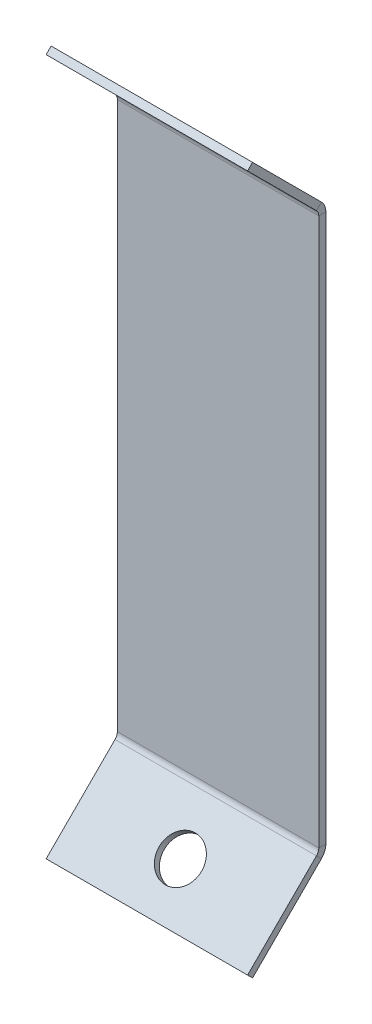
SolidWorks part; units mm, degrees
note: The reader was unsure of these and kept them because the rebuilt part matched: flange length of "Edge-Flange1", "Edge-Flange2".
ref_plane "Front Plane" through (0, 0, 0) normal (0, 0, 1) x (1, 0, 0)
ref_plane "Top Plane" through (0, 0, 0) normal (0, 1, 0) x (1, 0, 0)
ref_plane "Right Plane" through (0, 0, 0) normal (1, 0, 0) x (0, 0, -1)
sketch "Sketch1" plane through (0, 0, 0) normal (0, 0, 1) x (1, 0, 0)
  line L0 (10, 27.5) -> (-10, -27.5) construction
  line L1 (10, 27.5) -> (-10, 27.5)
  line L2 (10, 27.5) -> (10, -27.5)
  line L3 (10, -27.5) -> (-10, -27.5)
  line L4 (-10, 27.5) -> (-10, -27.5)
  point P4 (0, 0)
  dimension "D1" = 20
  dimension "D2" = 55
base flange "Base-Flange1" sketch "Sketch1" thickness 0.7 reverse thickness direction no parameters "D1"=0.8
edge flange "Edge-Flange1" sketch "Sketch8" flange angle 135 flange length 10 flange position material outside bend radius 0.8 thickness 0.7 parameters "D1"=3, "D6"=10
sketch "Sketch8" plane through (0, -27.5, 0) normal (0, -0.7071, -0.7071) x (1, 0, 0)
  line L0 (-10, 0) -> (10, 0) construction
  line L1 (-10, 0) -> (10, 0)
  line L2 (-10, 0) -> (-10, 10)
  line L3 (-10, 10) -> (10, 10)
  line L4 (10, 10) -> (10, 0)
bend "EdgeBend1" bend radius 0.8 bend angle 45 parameters "D5"=1
edge flange "Edge-Flange2" sketch "Sketch11" flange angle 135 flange length 10 flange position material outside bend radius 0.8 thickness 0.7 parameters "D1"=3, "D6"=10
sketch "Sketch11" plane through (0, 27.5, 0) normal (0, 0.7071, -0.7071) x (-1, 0, 0)
  line L2 (-10, 0) -> (-10, 10)
  line L3 (-10, 10) -> (10, 10)
  line L4 (10, 10) -> (10, 0)
  line L5 (-10, 0) -> (10, 0) construction
  line L6 (-10, 0) -> (10, 0)
bend "EdgeBend2" bend radius 0.8 bend angle 45 parameters "D5"=2
hole_wizard "#19 (0.166) Diameter Slot1" positions "Sketch13" profile "Sketch12" size "#19" standard "ANSI Inch" slot yes end condition through all
sketch "Sketch13" plane through (0, -13.75, -13.75) normal (0, 0.7071, 0.7071) x (1, 0, 0)
  point P0 (0, -24.7388)
sketch "Sketch12" plane through (0, -31.243, 3.743) normal (1, 0, 0) x (0, -0.7071, 0.7071)
  line L0 (0, 0) -> (0, 5.845)
  line L1 (0, 5.845) -> (2.1082, 5.845)
  line L2 (2.1082, 5.845) -> (2.1082, 0)
  line L5 (2.1082, 0) -> (0, 0)
  line L11 (0, -6.35) -> (0, 107.95) construction
  dimension "Thru Hole Dia." = 4.2164
  dimension "Thru Hole Depth" = 5.845
hole_wizard "#19 (0.166) Diameter Slot2" positions "Sketch15" profile "Sketch14" size "#19" standard "ANSI Inch" slot yes end condition through all
sketch "Sketch15" plane through (0, 13.75, -13.75) normal (0, -0.7071, 0.7071) x (1, 0, 0)
  point P0 (0, 24.9402)
sketch "Sketch14" plane through (0, 31.3854, 3.8854) normal (1, 0, 0) x (0, -0.7071, -0.7071)
  line L0 (0, 0) -> (0, 5.845)
  line L1 (0, 5.845) -> (2.1082, 5.845)
  line L2 (2.1082, 5.845) -> (2.1082, 0)
  line L5 (2.1082, 0) -> (0, 0)
  line L11 (0, -6.35) -> (0, 107.95) construction
  dimension "Thru Hole Dia." = 4.2164
  dimension "Thru Hole Depth" = 5.845
sketch "Bend-Lines1" plane through (0, 0, 0) normal (0, 1, 0) x (1, 0, 0)
sketch "Bounding-Box1" plane through (0, 0, 0) normal (0, 1, 0) x (1, 0, 0)
sheet metal parameters "Sheet-Metal1" thickness 0.7 parameters "D1"=3
flat pattern "Flat-Pattern1" [suppressed]
sketch "Bend-Lines2" plane through (0, 0, 0) normal (0, 1, 0) x (1, 0, 0)
sketch "Bounding-Box2" [suppressed] plane through (0, 0, 0) normal (0, 1, 0) x (1, 0, 0)
sheet metal parameters "Sheet-Metal2" thickness 0.7 parameters "D1"=3
flat pattern "Flat-Pattern1" [suppressed]
sketch "Bend-Lines2" plane through (0, 0, 0) normal (0, 1, 0) x (1, 0, 0)
sketch "Bounding-Box2" [suppressed] plane through (0, 0, 0) normal (0, 1, 0) x (1, 0, 0)
bend of the flat pattern "Flatten-<EdgeBend1>1"
sheet metal parameters "Sheet-Metal3" thickness 0.7 parameters "D1"=3
flat pattern "Flat-Pattern1" [suppressed]
sketch "Bend-Lines2" plane through (0, 0, 0) normal (0, 1, 0) x (1, 0, 0)
sketch "Bounding-Box2" [suppressed] plane through (0, 0, 0) normal (0, 1, 0) x (1, 0, 0)
bend of the flat pattern "Flatten-<EdgeBend1>1"
bend of the flat pattern "Flatten-<EdgeBend2>1"
sheet metal parameters "Sheet-Metal4" thickness 0.7 parameters "D1"=3
flat pattern "Flat-Pattern1" [suppressed]
sketch "Bend-Lines2" plane through (0, 0, 0) normal (0, 1, 0) x (1, 0, 0)
sketch "Bounding-Box2" [suppressed] plane through (0, 0, 0) normal (0, 1, 0) x (1, 0, 0)
bend of the flat pattern "Flatten-<EdgeBend1>1"
bend of the flat pattern "Flatten-<EdgeBend2>1"
sheet metal parameters "Sheet-Metal5" thickness 0.7 parameters "D1"=3
flat pattern "Flat-Pattern1" [suppressed]
sketch "Bend-Lines2" plane through (0, 0, 0) normal (0, 1, 0) x (1, 0, 0)
sketch "Bounding-Box2" [suppressed] plane through (0, 0, 0) normal (0, 1, 0) x (1, 0, 0)
bend of the flat pattern "Flatten-<EdgeBend1>1"
bend of the flat pattern "Flatten-<EdgeBend2>1"
